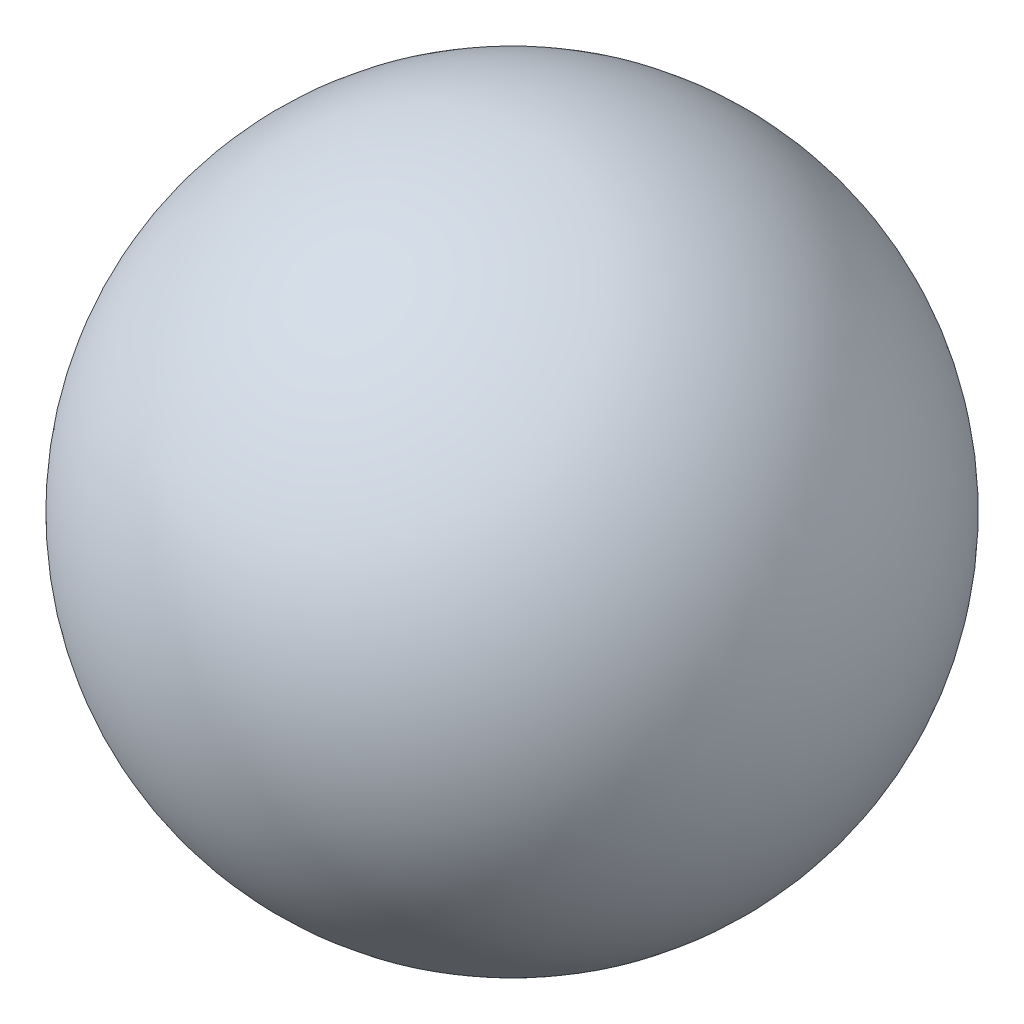
SolidWorks part; units mm, degrees
ref_plane "Front Plane" through (0, 0, 0) normal (0, 0, 1) x (1, 0, 0)
ref_plane "Top Plane" through (0, 0, 0) normal (0, 1, 0) x (1, 0, 0)
ref_plane "Right Plane" through (0, 0, 0) normal (1, 0, 0) x (0, 0, -1)
sketch "Sketch1" plane through (0, 0, 0) normal (0, 0, 1) x (1, 0, 0)
  line L0 (0, 2.7781) -> (0, -2.7781)
  arc A0 (0, -2.7781) -> (0, 2.7781) centre (0, 0) ccw
  dimension "D1" = 5.5563
ref_axis "Axis1" through (0, 0, 0) along (0, 1, 0)
revolve "Revolve3" add sketch "Sketch1" angle 360 about L0
